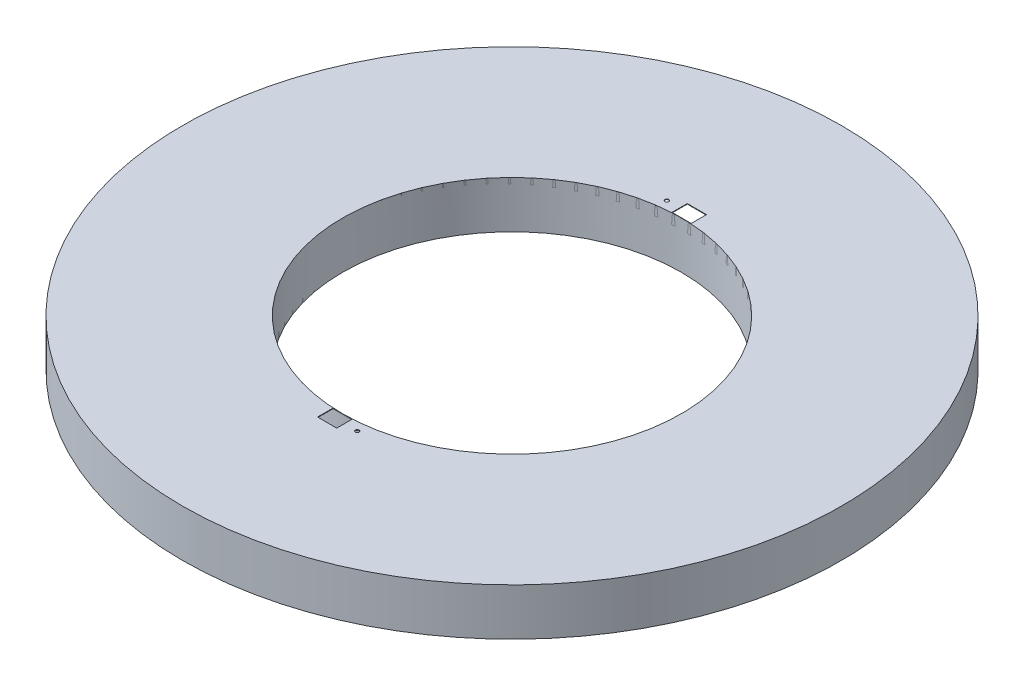
SolidWorks part; units mm, degrees
material "1345 Alloy"
ref_plane "Front Plane" through (0, 0, 0) normal (0, 0, 1) x (1, 0, 0)
ref_plane "Top Plane" through (0, 0, 0) normal (0, 1, 0) x (1, 0, 0)
ref_plane "Right Plane" through (0, 0, 0) normal (1, 0, 0) x (0, 0, -1)
sketch "Sketch1" plane through (0, 0, 0) normal (0, 1, 0) x (1, 0, 0)
  circle A0 centre (0, 0) radius 1750
extrude "Boss-Extrude1" add sketch "Sketch1" along normal blind 500
sketch "Sketch2" plane through (0, 500, 0) normal (0, 1, 0) x (1, 0, 0)
  circle A0 centre (0, 0) radius 900
extrude "Cut-Extrude2" cut sketch "Sketch2" against normal blind 300
sketch "Sketch3" plane through (0, 0, 0) normal (0, -1, 0) x (1, 0, 0)
  circle A0 centre (0, 0) radius 600
extrude "Cut-Extrude3" cut sketch "Sketch3" against normal blind 300
sketch "Sketch4" plane through (0, 0, 0) normal (0, -1, 0) x (-1, 0, 0)
  circle A0 centre (0, 0) radius 900.75
  circle A1 centre (0, 0) radius 1748.5
extrude "Cut-Extrude5" cut sketch "Sketch4" against normal blind 497
sketch "Sketch5" plane through (0, 0, 0) normal (0, 0, 1) x (1, 0, 0)
  line L0 (0, 0) -> (0, 250)
  line L1 (0, 250) -> (1750, 250)
  line L2 (1750, 0) -> (1750, 500) construction
  line L3 (1750, 250) -> (1750, 0)
  line L4 (1750, 0) -> (-1750, 0)
  line L5 (-1750, 0) -> (-1750, 250)
  line L6 (-1750, 500) -> (-1750, 0) construction
  line L7 (-1750, 250) -> (0, 250)
extrude "Cut-Extrude6" cut sketch "Sketch5" against normal through all both and the other way through all contours L7 L5 L4 L0 | L4 L3 L1 L0 region at (-875, 125, 0) region at (875, 125, 0)
sketch "Sketch6" plane through (0, 497, 0) normal (0, -1, 0) x (1, 0, 0)
  line L0 (0, 900.75) -> (51, 900.75)
  line L1 (51, 900.75) -> (51, 981.75)
  line L2 (51, 981.75) -> (-51, 981.75)
  line L3 (-51, 981.75) -> (-51, 900.75)
  line L4 (-51, 900.75) -> (0, 900.75)
  circle A0 centre (0, 0) radius 900.75 construction
  circle A1 centre (0, 0) radius 900.75 construction
extrude "Cut-Extrude7" cut sketch "Sketch6" against normal blind 10
pattern_circular "CirPattern1" count 2 every 180 about axis through (0, 497, 0) along (0, -1, 0) of "Cut-Extrude7" reverse direction yes
sketch "Sketch7" plane through (0, 497, 0) normal (0, -1, 0) x (1, 0, 0)
  circle A0 centre (-118.8186, -941.25) radius 10
  circle A1 centre (119.3007, 941.189) radius 10
  point P2 (0, 0)
  point P3 (-118.8186, -941.25)
  point P4 (0, 0)
  point P7 (0, 0)
  dimension "D1" = 2
extrude "Cut-Extrude8" cut sketch "Sketch7" against normal blind 10
